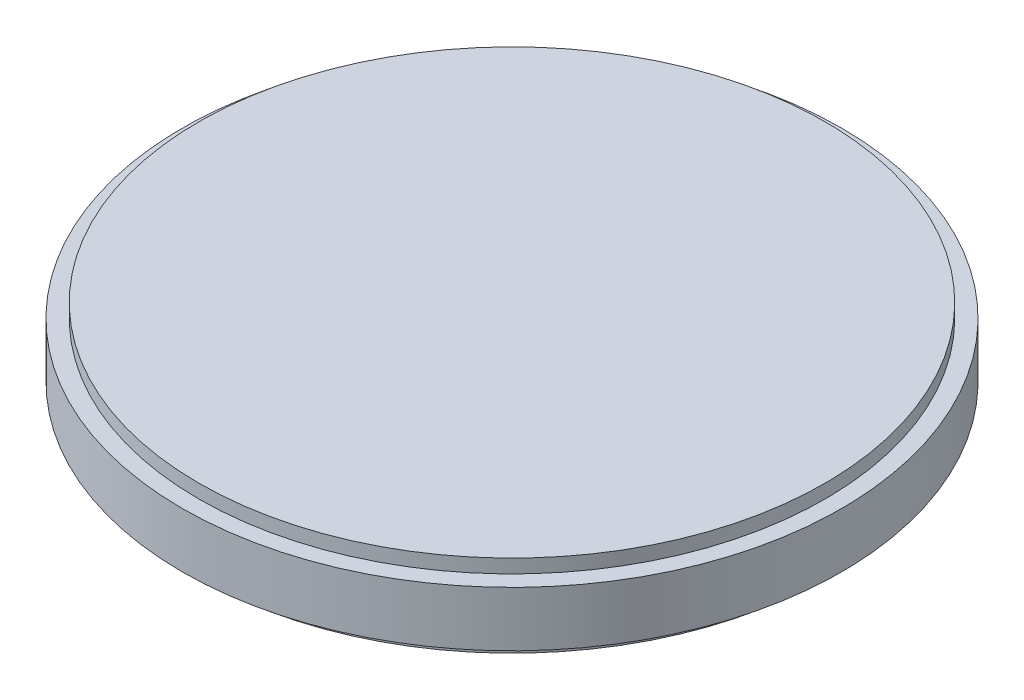
SolidWorks part; units mm, degrees
ref_plane "Front Plane" through (0, 0, 0) normal (0, 0, 1) x (1, 0, 0)
ref_plane "Top Plane" through (0, 0, 0) normal (0, 1, 0) x (1, 0, 0)
ref_plane "Right Plane" through (0, 0, 0) normal (1, 0, 0) x (0, 0, -1)
sketch "Sketch1" plane through (0, 0, 0) normal (0, 1, 0) x (1, 0, 0)
  circle A0 centre (0, 0) radius 57
  circle A1 centre (0, 0) radius 60
  dimension "D1" = 120
  dimension "D2" = 114
extrude "Extrude4" add sketch "Sketch1" along normal mid plane 15 contours A0
extrude "Extrude5" add sketch "Sketch" along normal mid plane 10
sketch "Sketch" plane through (0, 0, 0) normal (0, 1, 0) x (1, 0, 0) same geometry as "Sketch1"
